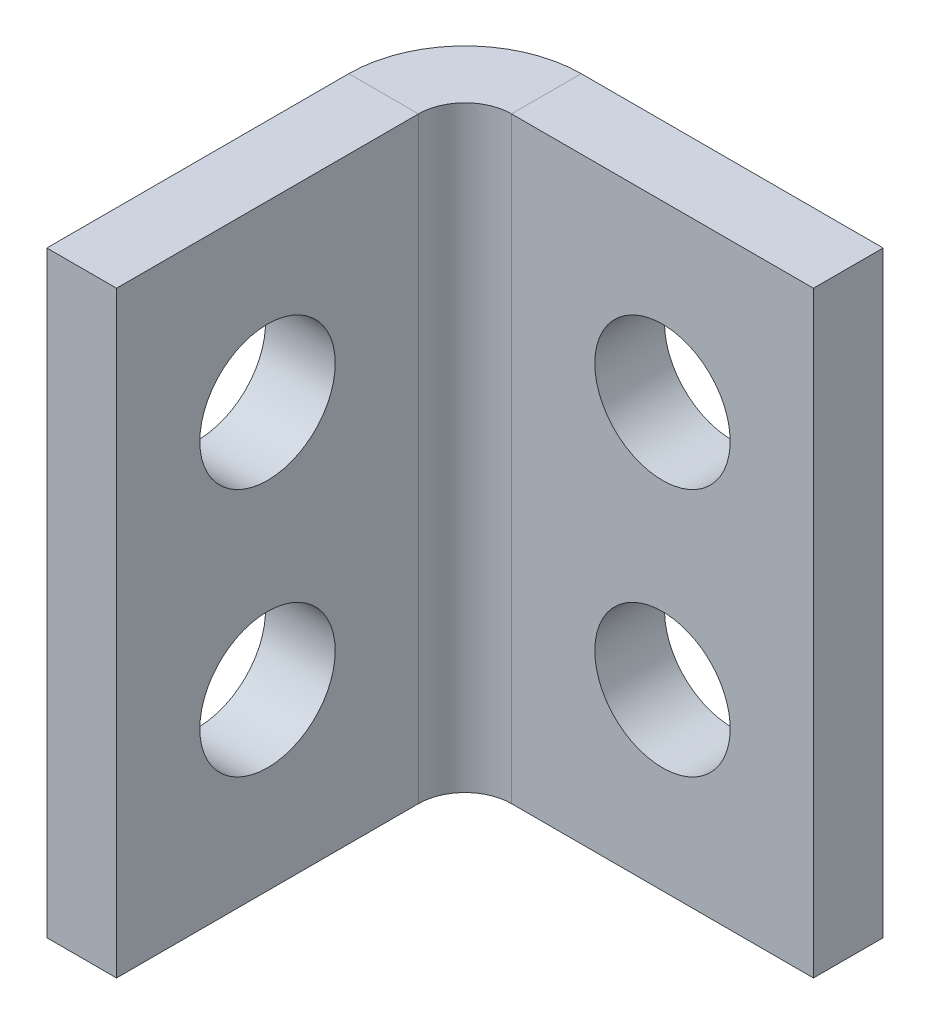
SolidWorks part; units mm, degrees
note: The reader was unsure of these and kept them because the rebuilt part matched: thickness of "Base-Flange1", "Edge-Flange1", "Sheet-Metal1", "Sheet-Metal2", "Sheet-Metal3"; flange length of "Edge-Flange1".
ref_plane "Front Plane" through (0, 0, 0) normal (0, 0, 1) x (1, 0, 0)
ref_plane "Top Plane" through (0, 0, 0) normal (0, 1, 0) x (1, 0, 0)
ref_plane "Right Plane" through (0, 0, 0) normal (1, 0, 0) x (0, 0, -1)
sketch "Sketch1" plane through (0, 0, 0) normal (0, 0, 1) x (1, 0, 0)
  line L1 (0, 0) -> (8.75, 0)
  line L2 (0, 0) -> (0, 15)
  line L3 (0, 15) -> (8.75, 15)
  line L4 (8.75, 0) -> (8.75, 15)
  dimension "D1" = 8.75
  dimension "D2" = 15
base flange "Base-Flange1" sketch "Sketch1" thickness 1.75 reverse thickness direction no parameters "D1"=1.1684
edge flange "Edge-Flange1" sketch "Sketch8" flange angle 90 flange length 8.75 flange position material outside bend radius 1.1684 thickness 1.75 relief rectangular parameters "D1"=1.016, "D6"=10
sketch "Sketch8" plane through (0, 0, 0) normal (-1, 0, 0) x (0, -1, 0)
  line L2 (-15, 0) -> (-15, 8.75)
  line L3 (-15, 8.75) -> (0, 8.75)
  line L4 (0, 8.75) -> (0, 0)
  line L7 (-15, 0) -> (0, 0) construction
  line L8 (-15, 0) -> (0, 0)
bend "EdgeBend1" bend radius 1.1684 bend angle 90 parameters "D5"=1
sketch "Sketch9" plane through (0, 0, -1.75) normal (0, 0, 1) x (1, 0, 0)
  line L0 (1.1684, 10.625) -> (8.75, 10.625) construction
  line L3 (4.9592, 10.625) -> (4.9592, 15) construction
  line L5 (1.1684, 4.375) -> (8.75, 4.375) construction
  line L6 (4.9592, 4.375) -> (4.9592, 0) construction
  line L8 (8.75, 15) -> (1.1684, 15) construction
  line L9 (8.75, 0) -> (8.75, 15) construction
  line L10 (1.1684, 0) -> (1.1684, 15) construction
  line L11 (1.1684, 0) -> (8.75, 0) construction
  dimension "D1" = 4.375
sketch "Sketch10" plane through (-1.75, 0, 0) normal (1, 0, 0) x (0, 0, -1)
  line L0 (-8.75, 10.625) -> (-1.1684, 10.625) construction
  line L3 (-4.9592, 10.625) -> (-4.9592, 15) construction
  line L5 (-8.75, 4.375) -> (-1.1684, 4.375) construction
  line L6 (-4.9592, 4.375) -> (-4.9592, 0) construction
  line L8 (-1.1684, 15) -> (-1.1684, 0) construction
  line L9 (-1.1684, 0) -> (-8.75, 0) construction
  line L10 (-8.75, 0) -> (-8.75, 15) construction
  line L11 (-8.75, 15) -> (-1.1684, 15) construction
  dimension "D1" = 4.375
hole_wizard "M3 Clearance Hole1" positions "3DSketch1" profile "Sketch11" hole size "M3" standard "ANSI Metric" end condition up to next
sketch3d "3DSketch1"
  point P0 (-1.75, 10.625, 4.9592)
  point P3 (4.9592, 10.625, -1.75)
  point P6 (4.9592, 4.375, -1.75)
  point P9 (-1.75, 4.375, 4.9592)
sketch "Sketch11" plane through (-1.75, 10.625, 4.9592) normal (0, 1, 0) x (0, 0, 1)
  line L0 (0, 0) -> (0, 1.75)
  line L1 (0, 1.75) -> (1.7, 1.75)
  line L2 (1.7, 1.75) -> (1.7, 0)
  line L5 (1.7, 0) -> (0, 0)
  line L11 (0, -6.35) -> (0, 107.95) construction
  dimension "Thru Hole Dia." = 3.4
  dimension "Thru Hole Depth" = 1.75
sketch "Bend-Lines1" [suppressed] plane through (0, 0, 0) normal (0, 1, 0) x (1, 0, 0)
sketch "Bounding-Box1" [suppressed] plane through (0, 0, 0) normal (0, 1, 0) x (1, 0, 0)
sheet metal parameters "Sheet-Metal1" thickness 1.75 parameters "D1"=1.016, "D7"=1.016
flat pattern "Flat-Pattern1" [suppressed]
sketch "Bend-Lines2" plane through (0, 0, 0) normal (0, 1, 0) x (1, 0, 0)
sketch3d "Bounding-Box2" [suppressed]
  line L0 (-8.75, 30, 0) -> (-8.75, 0, 0) construction
  line L1 (0, 30, 0) -> (0, 0, 0) construction
  line L2 (-8.75, 30, 0) -> (0, 30, 0) construction
  line L3 (-8.75, 0, 0) -> (0, 0, 0) construction
sheet metal parameters "Sheet-Metal2" thickness 1.75 parameters "D1"=1.016, "D7"=1.016
flat pattern "Flat-Pattern1"
sketch "Bend-Lines2" plane through (0, 0, 0) normal (0, 0, 1) x (1, 0, 0)
  line L0 (-0.1809, 30) -> (-0.1809, 0) construction
  line L1 (-0.1809, 30) -> (-0.1809, 0) construction
sketch3d "Bounding-Box2" [suppressed]
  line L0 (8.75, 30, 0) -> (8.75, 0, 0) construction
  line L1 (-9.1119, 30, 0) -> (-9.1119, 0, 0) construction
  line L2 (8.75, 30, 0) -> (-9.1119, 30, 0) construction
  line L3 (8.75, 0, 0) -> (-9.1119, 0, 0) construction
bend of the flat pattern "Flatten-<EdgeBend1>1"
sheet metal parameters "Sheet-Metal3" thickness 1.75 parameters "D1"=1.016, "D7"=1.016
flat pattern "Flat-Pattern1" [suppressed]
sketch "Bend-Lines2" plane through (0, 0, 0) normal (0, 0, 1) x (1, 0, 0)
  line L0 (-0.299, 15) -> (-0.299, 0) construction
  line L1 (-0.299, 15) -> (-0.299, 0) construction
sketch3d "Bounding-Box2" [suppressed]
  line L0 (-9.3481, 0, 0) -> (8.75, 0, 0) construction
  line L1 (-9.3481, 15, 0) -> (8.75, 15, 0) construction
  line L2 (-9.3481, 0, 0) -> (-9.3481, 15, 0) construction
  line L3 (8.75, 0, 0) -> (8.75, 15, 0) construction
bend of the flat pattern "Flatten-<EdgeBend1>1"
sketch "Sketch10-1" plane through (-0.5981, 0, -1.75) normal (0, 0, 1) x (1, 0, 0)
  line L0 (-8.75, 10.625) -> (-1.1684, 10.625) construction
  line L3 (-4.9592, 10.625) -> (-4.9592, 15) construction
  line L5 (-8.75, 4.375) -> (-1.1684, 4.375) construction
  line L6 (-4.9592, 4.375) -> (-4.9592, 0) construction
  dimension "D1" = 4.375
